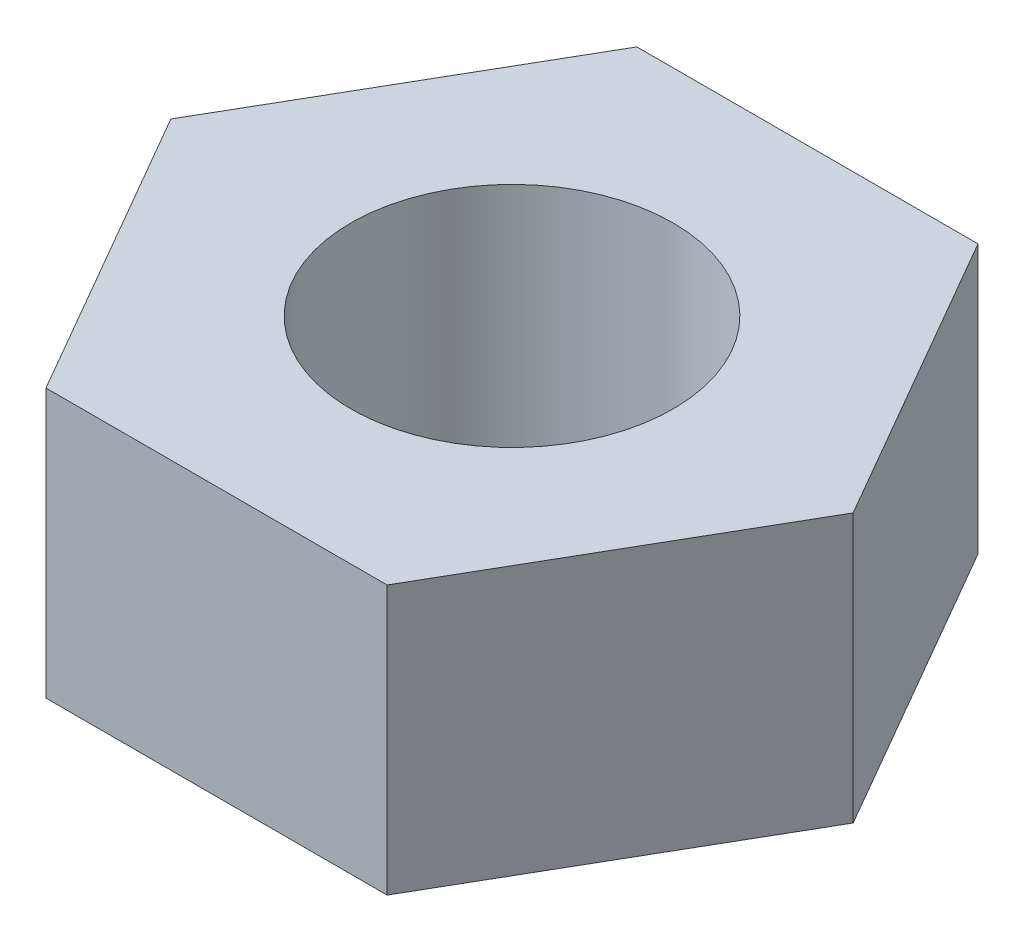
SolidWorks part; units mm, degrees
ref_plane "前视基准面" through (0, 0, 0) normal (0, 0, 1) x (1, 0, 0)
ref_plane "上视基准面" through (0, 0, 0) normal (0, 1, 0) x (1, 0, 0)
ref_plane "右视基准面" through (0, 0, 0) normal (1, 0, 0) x (0, 0, -1)
other "Configuration Table"
sketch "草图1" plane through (0, 0, 0) normal (0, 1, 0) x (1, 0, 0)
  line L1 (3.1754, 0) -> (1.5877, 2.75)
  line L2 (1.5877, 2.75) -> (-1.5877, 2.75)
  line L3 (-1.5877, 2.75) -> (-3.1754, 0)
  line L4 (-3.1754, 0) -> (-1.5877, -2.75)
  line L5 (-1.5877, -2.75) -> (1.5877, -2.75)
  line L6 (1.5877, -2.75) -> (3.1754, 0)
  circle A0 centre (0, 0) radius 2.75 construction
  dimension "D1" = 5.5
extrude "凸台-拉伸1" add sketch "草图1" along normal blind 2.5
sketch "草图3" plane through (0, 0, 0) normal (0, -1, 0) x (1, 0, 0)
  circle A0 centre (0, 0) radius 1.5
  dimension "D1" = 3
extrude "切除-拉伸1" cut sketch "草图3" against normal through all
ref_axis "基准轴1" through (0, 5.7881, 0) along (0, -1, 0)
